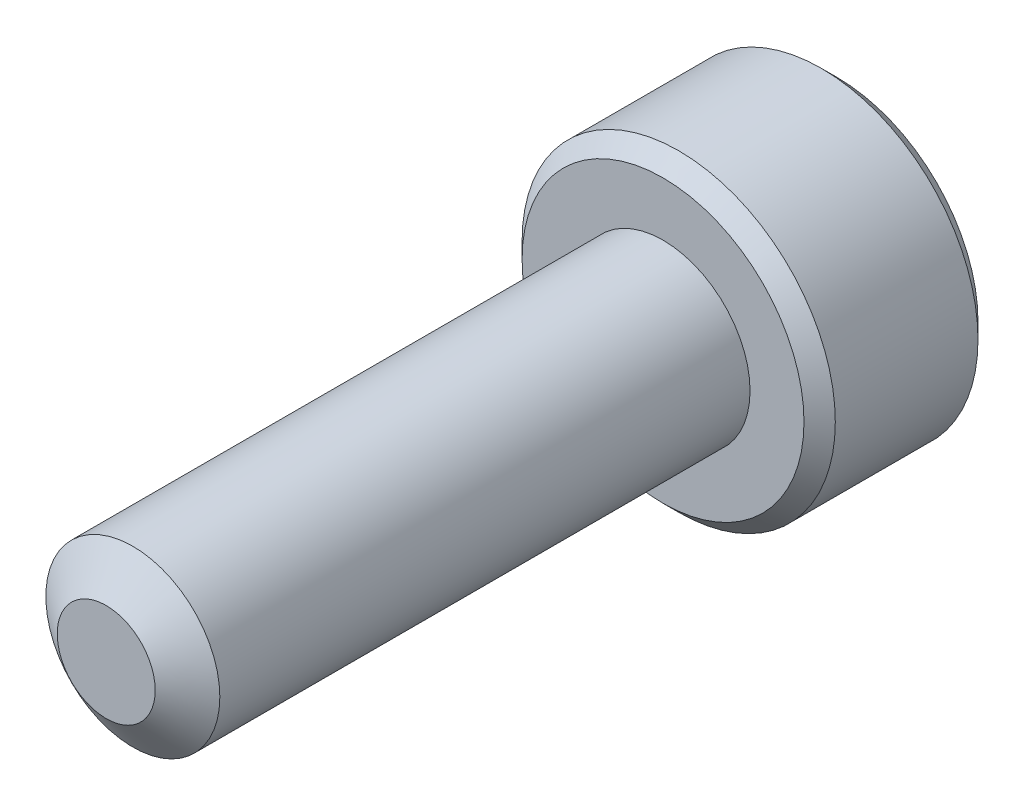
SolidWorks part; units mm, degrees
other "DetailItem1"
ref_plane "Front Plane" through (0, 0, 0) normal (0, 0, 1) x (1, 0, 0)
ref_plane "Top Plane" through (0, 0, 0) normal (0, 1, 0) x (1, 0, 0)
ref_plane "Right Plane" through (0, 0, 0) normal (1, 0, 0) x (0, 0, -1)
sketch "Sketch1" plane through (0, 0, 0) normal (0, 0, 1) x (1, 0, 0)
  circle A0 centre (0, 0) radius 1.25
  dimension "OD" = 2.5
extrude "Extrude1" add sketch "Sketch1" against normal blind 8
sketch "Sketch2" plane through (0, 0, 0) normal (0, 0, 1) x (1, 0, 0)
  circle A0 centre (0, 0) radius 1.25 construction
  circle A1 centre (0, 0) radius 1.25
curve "Helix/Spiral1" pitch 0.45 height 8.45 turns 18.7778 parameters "pitch"=0.45
sketch "Sketch3" plane through (0, 0, 0) normal (1, 0, 0) x (0, 0, -1)
  line L0 (-0.3937, 1.25) -> (-0.225, 0.9577)
  line L1 (-0.225, 0.9577) -> (-0.1688, 0.9577)
  line L2 (-0.1688, 0.9577) -> (0, 1.25)
  line L3 (-0.3937, 1.25) -> (0, 1.25)
  line L4 (-0.1969, 1.25) -> (-0.1969, 0.9577) construction
  line L5 (-0.3094, 1.1039) -> (-0.0844, 1.1039) construction
  line L6 (0, 1.25) -> (0, -1.25) construction
  dimension "D2" = 0.225
  dimension "D3" = 60
sweep "Cut-Sweep1" [suppressed] cut profiles "Sketch3" path "Helix/Spiral1"
sketch "Sketch4" plane through (0, 0, 0) normal (1, 0, 0) x (0, 0, -1)
  line L0 (0.3825, 1.25) -> (0, 0.7037)
  line L1 (0, 0.7037) -> (0, 1.25)
  line L2 (0.3825, 1.25) -> (0, 1.25)
  line L3 (-0.3937, 1.25) -> (0, 1.25) construction
  line L4 (0, 0) -> (7.0209, 0) construction
  dimension "D1" = 55
  dimension "D2" = 0.254
revolve "Cut-Revolve1" cut sketch "Sketch4" angle 360 about L4
sketch "Sketch6" plane through (0, 0, -8) normal (0, 0, -1) x (-1, 0, 0)
  circle A0 centre (0, 0) radius 2.25
  dimension "head dia" = 4.5
extrude "Extrude2" add sketch "Sketch6" along normal blind 2.5
sketch "Sketch7" plane through (0, 0, -10.5) normal (0, 0, -1) x (-1, 0, 0)
  line L1 (0, 1.1547) -> (-1, 0.5774)
  line L2 (-1, 0.5774) -> (-1, -0.5774)
  line L3 (-1, -0.5774) -> (0, -1.1547)
  line L4 (0, -1.1547) -> (1, -0.5774)
  line L5 (1, -0.5774) -> (1, 0.5774)
  line L6 (1, 0.5774) -> (0, 1.1547)
  circle A0 centre (0, 0) radius 1 construction
  dimension "hex dia" = 2
extrude "Cut-Extrude1" cut sketch "Sketch7" against normal blind 1.5
sketch "Sketch8" plane through (0, 0, -10.5) normal (0, 0, -1) x (-1, 0, 0)
  circle A0 centre (0, 0) radius 1.1547
extrude "Cut-Extrude2" cut sketch "Sketch8" against normal through all draft 45
chamfer "Chamfer1" distance 0.225 angle 45 2 edges at (-2.25, 0, -10.5) (-2.25, 0, -8)
sketch "Sketch10" plane through (0, 0, -8) normal (0, 0, 1) x (1, 0, 0)
  circle A1 centre (0, 0) radius 1.25
  circle A2 centre (0, 0) radius 1.25
  dimension "D1" = 0
ref_plane "Plane1" through (0, 0, 0) normal (0, 0, 1) x (1, 0, 0)
extrude "partial thread" [suppressed] add sketch "Sketch10" along normal up to surface (8 mm away) separate body up to plane "Plane1"
chamfer "Chamfer2" [suppressed] distance 0.05 angle 45
combine bodies "Combine1" [suppressed] operation type add bodies to combine 107 108
sketch "Sketch9" plane through (0, 0, 0) normal (1, 0, 0) x (0, 0, -1)
  line L0 (0, 1.25) -> (0, -1.25) construction
  line L1 (1.125, 1.25) -> (1.125, -1.25) construction
  dimension "D1" = 1.125
equation "\"D3@Helix/Spiral1\" = \"screw length@Extrude1\"+\"pitch@Helix/Spiral1\""
equation "\"D1@Sketch3\" = \"pitch@Helix/Spiral1\"*.125"
equation "\"D2@Sketch3\" = \"pitch@Helix/Spiral1\"*.5"
equation "\"D1@Cut-Extrude1\" = \"hex dia@Sketch7\"*.75"
equation "\"D1@Chamfer1\" = \"head dia@Sketch6\"*.05"
equation "\"D1@Sketch9\" = \"pitch@Helix/Spiral1\"*2.5"
equation "\"D1@Chamfer2\"=\"OD@Sketch1\"*.02"
